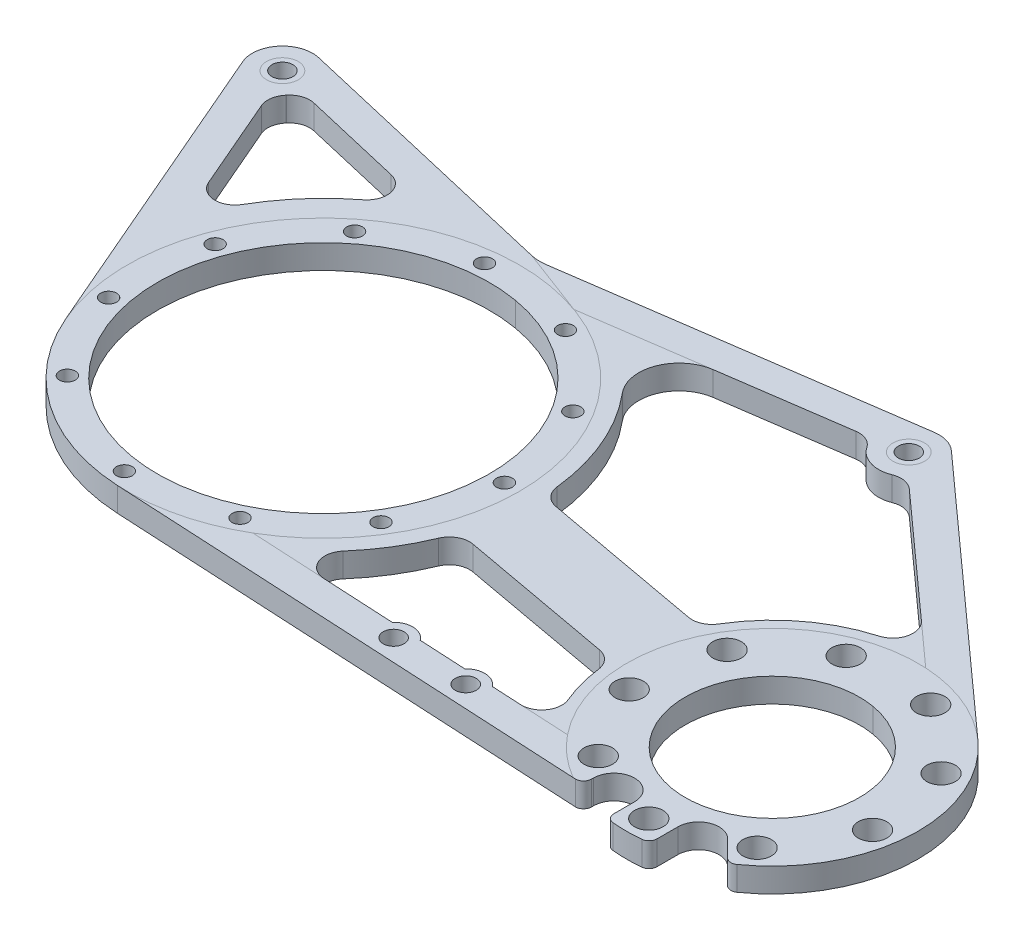
SolidWorks part; units mm, degrees
material "6061-T6 (SS)"
ref_plane "X-Y Datum" through (0, 0, 0) normal (0, 0, 1) x (1, 0, 0)
ref_plane "X-Z Datum" through (0, 0, 0) normal (0, 1, 0) x (1, 0, 0)
ref_plane "Y-Z Datum" through (0, 0, 0) normal (1, 0, 0) x (0, 0, -1)
sketch "Sketch2" plane through (0, 31.3819, 0) normal (0, 1, 0) x (1, 0, 0)
  line L0 (-693.7583, -176.702) -> (-693.7583, -183.2747) construction
  line L1 (-680.0808, -183.2747) -> (-680.0808, -176.702) construction
  line L2 (-668.9846, -172.1058) -> (-663.7197, -177.3707) construction
  line L3 (-693.7583, -176.702) -> (-693.7583, -183.2747)
  line L4 (-680.0808, -183.2747) -> (-680.0808, -176.702)
  line L5 (-668.9846, -172.1058) -> (-663.7197, -177.3707)
  line L6 (-966.641, -0.354) -> (-738.041, -0.354)
  line L7 (-727.7656, -5.5904) -> (-649.7224, -113.0358)
  line L9 (-977.8288, -19.0644) -> (-913.2312, -139.3061)
  line L10 (-706.7583, -177.279) -> (-706.7583, -176.702) construction
  line L11 (-706.7583, -177.279) -> (-706.7583, -176.702)
  line L12 (-861.9259, -171.8334) -> (-709.2983, -179.819)
  line L13 (-858.691, -110.0055) -> (-686.9195, -140.054) construction
  line L14 (-972.26, -24.9963) -> (-955.4664, -39.59) construction
  line L15 (-941.4162, -26.937) -> (-954.1775, -8.712) construction
  line L16 (-751.1929, -14.159) -> (-755.4346, -35.9995) construction
  line L17 (-737.4517, -41.8408) -> (-728.049, -21.6768) construction
  line L18 (-972.26, -24.9963) -> (-955.4664, -39.59)
  line L19 (-941.4162, -26.937) -> (-954.1775, -8.712)
  line L20 (-751.1929, -14.159) -> (-755.4346, -35.9995)
  line L21 (-737.4517, -41.8408) -> (-728.049, -21.6768)
  line L22 (-949.2186, -22.8753) -> (-746.0843, -28.2904)
  line L23 (-739.7146, -30.7335) -> (-656.1751, -105.8723)
  line L24 (-957.9647, -36.1729) -> (-915.5404, -134.527)
  arc A0 (-710.607, -179.4559) -> (-706.7583, -177.279) centre (-709.2983, -177.279) ccw construction
  arc A1 (-693.7583, -176.702) -> (-706.7583, -176.702) centre (-700.2583, -176.702) ccw construction
  arc A2 (-693.7583, -183.2747) -> (-691.4697, -185.8023) centre (-691.2183, -183.2747) ccw construction
  arc A3 (-691.4697, -185.8023) -> (-682.3694, -185.8023) centre (-686.9195, -140.054) ccw construction
  arc A4 (-682.3694, -185.8023) -> (-680.0808, -183.2747) centre (-682.6208, -183.2747) ccw construction
  arc A5 (-668.9846, -172.1058) -> (-680.0808, -176.702) centre (-673.5808, -176.702) ccw construction
  arc A6 (-663.7197, -177.3707) -> (-660.4619, -177.6519) centre (-661.9236, -175.5746) ccw construction
  arc A7 (-660.4619, -177.6519) -> (-710.607, -179.4559) centre (-686.9195, -140.054) ccw construction
  circle A8 centre (-858.691, -110.0055) radius 52.3875 construction
  circle A9 centre (-858.691, -110.0055) radius 61.9125 construction
  circle A10 centre (-738.041, -13.054) radius 12.7 construction
  circle A11 centre (-966.641, -13.054) radius 12.7 construction
  arc A12 (-710.607, -179.4559) -> (-706.7583, -177.279) centre (-709.2983, -177.279) ccw
  arc A13 (-693.7583, -176.702) -> (-706.7583, -176.702) centre (-700.2583, -176.702) ccw
  arc A14 (-693.7583, -183.2747) -> (-691.4697, -185.8023) centre (-691.2183, -183.2747) ccw
  arc A15 (-691.4697, -185.8023) -> (-682.3694, -185.8023) centre (-686.9195, -140.054) ccw
  arc A16 (-682.3694, -185.8023) -> (-680.0808, -183.2747) centre (-682.6208, -183.2747) ccw
  arc A17 (-668.9846, -172.1058) -> (-680.0808, -176.702) centre (-673.5808, -176.702) ccw
  arc A18 (-663.7197, -177.3707) -> (-660.4619, -177.6519) centre (-661.9236, -175.5746) ccw
  arc A19 (-660.4619, -177.6519) -> (-710.607, -179.4559) centre (-686.9195, -140.054) ccw
  circle A20 centre (-858.691, -110.0055) radius 52.3875
  circle A21 centre (-858.691, -110.0055) radius 61.9125
  circle A22 centre (-738.041, -13.054) radius 12.7
  circle A23 centre (-966.641, -13.054) radius 12.7
  circle A31 centre (-864.6648, -166.8424) radius 2.5 construction
  circle A39 centre (-864.6648, -166.8424) radius 2.5
  circle A40 centre (-686.9195, -140.054) radius 27.4955 construction
  circle A41 centre (-686.9195, -140.054) radius 27.4955
  circle A42 centre (-711.9883, -169.9297) radius 4.5 construction
  circle A43 centre (-725.3271, -146.8263) radius 4.5 construction
  circle A44 centre (-720.6945, -120.554) radius 4.5 construction
  circle A45 centre (-700.2583, -103.406) radius 4.5 construction
  circle A46 centre (-673.5808, -103.406) radius 4.5 construction
  circle A47 centre (-653.1446, -120.554) radius 4.5 construction
  circle A48 centre (-648.512, -146.8263) radius 4.5 construction
  circle A49 centre (-661.8508, -169.9297) radius 4.5 construction
  circle A50 centre (-686.9195, -179.054) radius 4.5 construction
  circle A51 centre (-711.9883, -169.9297) radius 4.5
  circle A52 centre (-725.3271, -146.8263) radius 4.5
  circle A53 centre (-720.6945, -120.554) radius 4.5
  circle A54 centre (-700.2583, -103.406) radius 4.5
  circle A55 centre (-673.5808, -103.406) radius 4.5
  circle A56 centre (-653.1446, -120.554) radius 4.5
  circle A57 centre (-648.512, -146.8263) radius 4.5
  circle A58 centre (-661.8508, -169.9297) radius 4.5
  circle A59 centre (-686.9195, -179.054) radius 4.5
  circle A60 centre (-966.641, -13.054) radius 3.3
  circle A61 centre (-738.041, -13.054) radius 3.3
  arc A62 (-955.4664, -39.59) -> (-941.4162, -26.937) centre (-949.2186, -32.4003) ccw construction
  arc A63 (-749.3237, -37.1863) -> (-742.8448, -38.4445) centre (-746.0843, -37.8154) ccw construction
  arc A64 (-742.8448, -38.4445) -> (-749.3237, -37.1863) centre (-746.0843, -37.8154) ccw construction
  arc A65 (-755.4346, -35.9995) -> (-737.4517, -41.8408) centre (-746.0843, -37.8154) ccw construction
  arc A66 (-955.4664, -39.59) -> (-941.4162, -26.937) centre (-949.2186, -32.4003) ccw
  arc A67 (-749.3237, -37.1863) -> (-742.8448, -38.4445) centre (-746.0843, -37.8154) ccw
  arc A68 (-742.8448, -38.4445) -> (-749.3237, -37.1863) centre (-746.0843, -37.8154) ccw
  arc A69 (-755.4346, -35.9995) -> (-737.4517, -41.8408) centre (-746.0843, -37.8154) ccw
  circle A70 centre (-949.2186, -32.4003) radius 3.3
  circle A71 centre (-949.2186, -32.4003) radius 9.525
  circle A72 centre (-746.0843, -37.8154) radius 9.525
  point P94 (-949.2186, -32.4003)
  dimension "D1" = 6.6
  dimension "D2" = 6.6
  dimension "D3" = 6.6
extrude "Boss-Extrude1" add sketch "Sketch2" along normal blind 7.62 contours A21 A39 A20 | A18 A19 A12 L11 A13 L3 A14 A15 A16 L4 A17 L5 A59 A58 A57 A56 A55 A54 A53 A52 A51 A41 | L13 A21 L12 A12 A19 | A21 L13 A19 L23 L21 A69 L20 L22 L19 A66 L18 L24 | A69 A72 A68 A67 | A72 L22 L20 | A72 L21 L23 | A71 L24 L18 | A71 L19 L22 | A71 A66 L22 A70 region at (-700.2583, 31.3819, 168.9016) region at (-773.051, 31.3819, 154.3682) region at (-890.9045, 31.3819, 160.8157) region at (-806.8861, 31.3819, 67.2042) region at (-956.9478, 31.3819, 38.0512) region at (-736.2382, 31.3819, 35.8095) region at (-956.6903, 31.3819, 37.8629) region at (-748.9437, 31.3819, 46.6182) region at (-752.4763, 31.3819, 29.8585) region at (-944.5842, 31.3819, 23.8004)
sketch "Sketch3" plane through (0, 31.3819, 0) normal (0, -1, 0) x (1, 0, 0)
  line L1 (-949.2186, 22.8753) -> (-746.0843, 28.2904) construction
  line L5 (-861.9259, 171.8334) -> (-709.2983, 179.819) construction
  line L6 (-977.8288, 19.0644) -> (-913.2312, 139.3061) construction
  line L7 (-727.7656, 5.5904) -> (-649.7224, 113.0358) construction
  line L13 (-751.1929, 14.159) -> (-755.4346, 35.9995) construction
  line L16 (-966.641, 0.354) -> (-738.041, 0.354) construction
  line L19 (-663.7197, 177.3707) -> (-668.9846, 172.1058)
  line L20 (-680.0808, 176.702) -> (-680.0808, 183.2747)
  line L21 (-693.7583, 183.2747) -> (-693.7583, 176.702)
  line L22 (-706.7583, 176.702) -> (-706.7583, 177.279)
  line L23 (-663.7197, 177.3707) -> (-668.9846, 172.1058)
  line L24 (-680.0808, 176.702) -> (-680.0808, 183.2747)
  line L25 (-693.7583, 183.2747) -> (-693.7583, 176.702)
  line L26 (-706.7583, 176.702) -> (-706.7583, 177.279)
  line L28 (-861.9259, 171.8334) -> (-709.2983, 179.819)
  line L29 (-977.8288, 19.0644) -> (-913.2312, 139.3061)
  line L30 (-727.7656, 5.5904) -> (-649.7224, 113.0358)
  line L31 (-966.641, 0.354) -> (-738.041, 0.354)
  line L34 (-737.4517, 41.8408) -> (-728.049, 21.6768) construction
  line L35 (-972.26, 24.9963) -> (-955.4664, 39.59) construction
  line L36 (-947.0539, 23.1246) -> (-856.9722, 44.1471)
  line L37 (-856.9722, 44.1471) -> (-747.4408, 28.3875)
  line L44 (-941.4162, 26.937) -> (-954.1775, 8.712) construction
  line L45 (-957.9647, 36.1729) -> (-915.5404, 134.527) construction
  line L46 (-739.7146, 30.7335) -> (-656.1751, 105.8723) construction
  line L47 (-861.9259, 171.8334) -> (-709.2983, 179.819)
  line L48 (-977.8288, 19.0644) -> (-913.2312, 139.3061)
  line L49 (-727.7656, 5.5904) -> (-649.7224, 113.0358)
  line L50 (-966.641, 0.354) -> (-738.041, 0.354)
  line L51 (-949.2186, 22.8753) -> (-746.0843, 28.2904)
  line L52 (-751.1929, 14.159) -> (-755.4346, 35.9995)
  line L53 (-737.4517, 41.8408) -> (-728.049, 21.6768)
  line L54 (-972.26, 24.9963) -> (-955.4664, 39.59)
  line L55 (-941.4162, 26.937) -> (-954.1775, 8.712)
  line L56 (-957.9647, 36.1729) -> (-915.5404, 134.527)
  line L57 (-739.7146, 30.7335) -> (-656.1751, 105.8723)
  arc A1 (-737.4517, 41.8408) -> (-755.4346, 35.9995) centre (-746.0843, 37.8154) ccw construction
  circle A3 centre (-966.641, 13.054) radius 12.7
  circle A5 centre (-966.641, 13.054) radius 12.7
  circle A7 centre (-738.041, 13.054) radius 12.7
  circle A9 centre (-738.041, 13.054) radius 12.7
  circle A11 centre (-858.691, 110.0055) radius 61.9125
  circle A13 centre (-858.691, 110.0055) radius 61.9125
  circle A15 centre (-858.691, 110.0055) radius 52.3875
  circle A17 centre (-858.691, 110.0055) radius 52.3875
  circle A19 centre (-686.9195, 140.054) radius 27.4955
  circle A21 centre (-686.9195, 140.054) radius 27.4955
  circle A23 centre (-864.6648, 166.8424) radius 2.5
  circle A25 centre (-864.6648, 166.8424) radius 2.5
  circle A51 centre (-720.6945, 120.554) radius 4.5
  circle A52 centre (-720.6945, 120.554) radius 4.5
  circle A68 centre (-725.3271, 146.8263) radius 4.5
  circle A69 centre (-725.3271, 146.8263) radius 4.5
  circle A70 centre (-711.9883, 169.9297) radius 4.5
  circle A71 centre (-711.9883, 169.9297) radius 4.5
  circle A72 centre (-738.041, 13.054) radius 3.3
  circle A73 centre (-738.041, 13.054) radius 3.3
  circle A74 centre (-966.641, 13.054) radius 3.3
  circle A75 centre (-966.641, 13.054) radius 3.3
  circle A76 centre (-686.9195, 179.054) radius 4.5
  circle A77 centre (-686.9195, 179.054) radius 4.5
  circle A78 centre (-661.8508, 169.9297) radius 4.5
  circle A79 centre (-661.8508, 169.9297) radius 4.5
  circle A80 centre (-648.512, 146.8263) radius 4.5
  circle A81 centre (-648.512, 146.8263) radius 4.5
  circle A82 centre (-653.1446, 120.554) radius 4.5
  circle A83 centre (-653.1446, 120.554) radius 4.5
  circle A84 centre (-673.5808, 103.406) radius 4.5
  circle A85 centre (-673.5808, 103.406) radius 4.5
  circle A86 centre (-700.2583, 103.406) radius 4.5
  circle A87 centre (-700.2583, 103.406) radius 4.5
  arc A95 (-710.607, 179.4559) -> (-660.4619, 177.6519) centre (-686.9195, 140.054) ccw
  arc A96 (-660.4619, 177.6519) -> (-663.7197, 177.3707) centre (-661.9236, 175.5746) ccw
  arc A97 (-680.0808, 176.702) -> (-668.9846, 172.1058) centre (-673.5808, 176.702) ccw
  arc A98 (-680.0808, 183.2747) -> (-682.3694, 185.8023) centre (-682.6208, 183.2747) ccw
  arc A99 (-682.3694, 185.8023) -> (-691.4697, 185.8023) centre (-686.9195, 140.054) ccw
  arc A100 (-691.4697, 185.8023) -> (-693.7583, 183.2747) centre (-691.2183, 183.2747) ccw
  arc A101 (-706.7583, 176.702) -> (-693.7583, 176.702) centre (-700.2583, 176.702) ccw
  arc A102 (-706.7583, 177.279) -> (-710.607, 179.4559) centre (-709.2983, 177.279) ccw
  arc A103 (-710.607, 179.4559) -> (-660.4619, 177.6519) centre (-686.9195, 140.054) ccw
  arc A104 (-660.4619, 177.6519) -> (-663.7197, 177.3707) centre (-661.9236, 175.5746) ccw
  arc A105 (-680.0808, 176.702) -> (-668.9846, 172.1058) centre (-673.5808, 176.702) ccw
  arc A106 (-680.0808, 183.2747) -> (-682.3694, 185.8023) centre (-682.6208, 183.2747) ccw
  arc A107 (-682.3694, 185.8023) -> (-691.4697, 185.8023) centre (-686.9195, 140.054) ccw
  arc A108 (-691.4697, 185.8023) -> (-693.7583, 183.2747) centre (-691.2183, 183.2747) ccw
  arc A109 (-706.7583, 176.702) -> (-693.7583, 176.702) centre (-700.2583, 176.702) ccw
  arc A110 (-706.7583, 177.279) -> (-710.607, 179.4559) centre (-709.2983, 177.279) ccw
  circle A152 centre (-746.0843, 37.8154) radius 9.525
  circle A153 centre (-746.0843, 37.8154) radius 9.525
  circle A154 centre (-949.2186, 32.4003) radius 9.525
  circle A155 centre (-949.2186, 32.4003) radius 9.525
  circle A156 centre (-949.2186, 32.4003) radius 3.3
  circle A157 centre (-949.2186, 32.4003) radius 3.3
  arc A158 (-941.4162, 26.937) -> (-955.4664, 39.59) centre (-949.2186, 32.4003) ccw construction
  arc A159 (-742.8448, 38.4445) -> (-749.3237, 37.1863) centre (-746.0843, 37.8154) ccw
  arc A160 (-749.3237, 37.1863) -> (-742.8448, 38.4445) centre (-746.0843, 37.8154) ccw
  arc A161 (-742.8448, 38.4445) -> (-749.3237, 37.1863) centre (-746.0843, 37.8154) ccw
  arc A162 (-749.3237, 37.1863) -> (-742.8448, 38.4445) centre (-746.0843, 37.8154) ccw
  arc A163 (-737.4517, 41.8408) -> (-755.4346, 35.9995) centre (-746.0843, 37.8154) ccw
  arc A164 (-941.4162, 26.937) -> (-955.4664, 39.59) centre (-949.2186, 32.4003) ccw
  dimension "D24" = 0
  dimension "D25" = 0
  dimension "D26" = 90.0818
  dimension "D27" = 21.0225
  dimension "D1" = 0
  dimension "D2" = 0
  dimension "D3" = 0
  dimension "D4" = 0
  dimension "D5" = 0
  dimension "D6" = 0
  dimension "D14" = 0
  dimension "D15" = 0
  dimension "D16" = 0
  dimension "D17" = 0
  dimension "D18" = 0
  dimension "D19" = 0
  dimension "D20" = 0
  dimension "D21" = 0
  dimension "D22" = 0
  dimension "D23" = 0
  dimension "D52" = 0
  dimension "D53" = 0
  dimension "D54" = 0
  dimension "D55" = 0
ref_point "Point1"
ref_point "Point2"
ref_plane "Plane1" through (-858.691, 31.3819, 110.0055) normal (0.985, 0, 0.1723) x (0.1723, 0, -0.985)
ref_plane "Plane2" through (-686.9195, 31.3819, 140.054) normal (-0.985, 0, -0.1723) x (-0.1723, 0, 0.985)
split line "Split Line1"
split line "Split Line2"
ref_axis "Axis1" through (-858.691, 39.0019, 110.0055) along (0, -1, 0)
ref_axis "Axis2" through (-686.9195, 39.0019, 140.054) along (0, -1, 0)
extrude "Cut-Extrude1" cut sketch "Sketch3" against normal through all contours L36 L55 L51 L52 L37 | A155 L51 L55 L36 | A153 L37 L52 L51 region at (-751.5495, 31.3819, 28.5688) region at (-850.6911, 31.3819, 31.7926) region at (-945.2616, 31.3819, 23.2848)
fillet "Fillet2" radius 12.7 1 edges at (-856.9722, 35.1919, 44.1471)
sketch "Sketch4" plane through (0, 31.3819, 0) normal (0, -1, 0) x (1, 0, 0)
  line L0 (-861.9259, 171.8334) -> (-709.2983, 179.819) construction
  line L1 (-727.7656, 5.5904) -> (-649.7224, 113.0358) construction
  line L2 (-977.8288, 19.0644) -> (-913.2312, 139.3061) construction
  line L4 (-706.7583, 176.702) -> (-706.7583, 177.279)
  line L5 (-663.7197, 177.3707) -> (-668.9846, 172.1058)
  line L6 (-680.0808, 176.702) -> (-680.0808, 183.2747)
  line L7 (-693.7583, 183.2747) -> (-693.7583, 176.702)
  line L8 (-706.7583, 176.702) -> (-706.7583, 177.279)
  line L9 (-663.7197, 177.3707) -> (-668.9846, 172.1058)
  line L10 (-680.0808, 176.702) -> (-680.0808, 183.2747)
  line L11 (-693.7583, 183.2747) -> (-693.7583, 176.702)
  line L13 (-966.641, 0.354) -> (-738.041, 0.354) construction
  line L14 (-861.9259, 171.8334) -> (-709.2983, 179.819)
  line L15 (-727.7656, 5.5904) -> (-649.7224, 113.0358)
  line L16 (-977.8288, 19.0644) -> (-913.2312, 139.3061)
  line L17 (-861.9259, 171.8334) -> (-709.2983, 179.819) construction
  line L19 (-966.641, 0.354) -> (-738.041, 0.354)
  line L20 (-924.6037, 87.863) -> (-948.1369, 33.3048)
  line L21 (-948.1369, 33.3048) -> (-888.5504, 47.2106)
  line L22 (-732.3805, 168.4374) -> (-812.7818, 164.2308) construction
  line L23 (-812.7818, 164.2308) -> (-733.9678, 114.3873) construction
  line L24 (-799.833, 147.0258) -> (-703.8013, 86.2934) construction
  line L25 (-703.8013, 86.2934) -> (-794.9695, 82.1785) construction
  line L26 (-824.108, 49.6832) -> (-755.4008, 39.7974) construction
  line L27 (-798.9847, 74.3695) -> (-701.5009, 78.7695) construction
  line L28 (-701.5009, 78.7695) -> (-739.4428, 44.643) construction
  line L29 (-977.8288, 19.0644) -> (-913.2312, 139.3061) construction
  line L30 (-727.7656, 5.5904) -> (-649.7224, 113.0358) construction
  line L31 (-966.641, 0.354) -> (-738.041, 0.354) construction
  line L32 (-663.7197, 177.3707) -> (-668.9846, 172.1058)
  line L33 (-680.0808, 176.702) -> (-680.0808, 183.2747)
  line L34 (-693.7583, 183.2747) -> (-693.7583, 176.702)
  line L35 (-706.7583, 176.702) -> (-706.7583, 177.279)
  line L36 (-663.7197, 177.3707) -> (-668.9846, 172.1058)
  line L37 (-680.0808, 176.702) -> (-680.0808, 183.2747)
  line L38 (-693.7583, 183.2747) -> (-693.7583, 176.702)
  line L39 (-706.7583, 176.702) -> (-706.7583, 177.279)
  line L40 (-949.2186, 22.8753) -> (-746.0843, 28.2904) construction
  line L41 (-751.1929, 14.159) -> (-755.4346, 35.9995) construction
  line L42 (-737.4517, 41.8408) -> (-728.049, 21.6768) construction
  line L43 (-972.26, 24.9963) -> (-955.4664, 39.59) construction
  line L44 (-941.4162, 26.937) -> (-954.1775, 8.712) construction
  line L45 (-957.9647, 36.1729) -> (-915.5404, 134.527) construction
  line L46 (-739.7146, 30.7335) -> (-656.1751, 105.8723) construction
  line L47 (-861.9259, 171.8334) -> (-709.2983, 179.819)
  line L48 (-977.8288, 19.0644) -> (-913.2312, 139.3061)
  line L49 (-727.7656, 5.5904) -> (-649.7224, 113.0358)
  line L50 (-966.641, 0.354) -> (-738.041, 0.354)
  line L51 (-949.2186, 22.8753) -> (-746.0843, 28.2904)
  line L52 (-751.1929, 14.159) -> (-755.4346, 35.9995)
  line L53 (-737.4517, 41.8408) -> (-728.049, 21.6768)
  line L54 (-972.26, 24.9963) -> (-955.4664, 39.59)
  line L55 (-941.4162, 26.937) -> (-954.1775, 8.712)
  line L56 (-957.9647, 36.1729) -> (-915.5404, 134.527)
  line L57 (-739.7146, 30.7335) -> (-656.1751, 105.8723)
  line L58 (-947.0539, 23.1246) -> (-859.3005, 43.6037) construction
  line L60 (-854.6056, 43.8066) -> (-747.4408, 28.3875) construction
  circle A1 centre (-858.691, 110.0055) radius 52.3875
  circle A2 centre (-858.691, 110.0055) radius 52.3875
  circle A3 centre (-858.691, 110.0055) radius 61.9125
  circle A4 centre (-858.691, 110.0055) radius 61.9125
  circle A5 centre (-738.041, 13.054) radius 12.7
  circle A6 centre (-738.041, 13.054) radius 12.7
  circle A7 centre (-966.641, 13.054) radius 12.7
  circle A8 centre (-966.641, 13.054) radius 12.7
  circle A17 centre (-864.6648, 166.8424) radius 2.5
  circle A18 centre (-864.6648, 166.8424) radius 2.5
  circle A19 centre (-686.9195, 140.054) radius 27.4955
  circle A20 centre (-686.9195, 140.054) radius 27.4955
  circle A21 centre (-725.3271, 146.8263) radius 4.5
  circle A22 centre (-725.3271, 146.8263) radius 4.5
  circle A23 centre (-720.6945, 120.554) radius 4.5
  circle A24 centre (-720.6945, 120.554) radius 4.5
  circle A31 centre (-661.8508, 169.9297) radius 4.5
  circle A32 centre (-661.8508, 169.9297) radius 4.5
  circle A33 centre (-686.9195, 179.054) radius 4.5
  circle A34 centre (-686.9195, 179.054) radius 4.5
  circle A35 centre (-966.641, 13.054) radius 3.3
  circle A36 centre (-966.641, 13.054) radius 3.3
  circle A37 centre (-738.041, 13.054) radius 3.3
  circle A38 centre (-738.041, 13.054) radius 3.3
  circle A39 centre (-711.9883, 169.9297) radius 4.5
  circle A40 centre (-711.9883, 169.9297) radius 4.5
  circle A41 centre (-700.2583, 103.406) radius 4.5
  circle A42 centre (-700.2583, 103.406) radius 4.5
  circle A43 centre (-673.5808, 103.406) radius 4.5
  circle A44 centre (-673.5808, 103.406) radius 4.5
  circle A45 centre (-653.1446, 120.554) radius 4.5
  circle A46 centre (-653.1446, 120.554) radius 4.5
  circle A47 centre (-648.512, 146.8263) radius 4.5
  circle A48 centre (-648.512, 146.8263) radius 4.5
  arc A49 (-888.5504, 47.2106) -> (-924.6037, 87.863) centre (-858.691, 110.0055) cw
  arc A50 (-732.3805, 168.4374) -> (-733.9678, 114.3873) centre (-686.9195, 140.054) ccw construction
  arc A51 (-799.833, 147.0258) -> (-794.9695, 82.1785) centre (-858.691, 110.0055) cw construction
  arc A52 (-824.108, 49.6832) -> (-798.9847, 74.3695) centre (-858.691, 110.0055) ccw construction
  arc A53 (-737.4517, 41.8408) -> (-755.4346, 35.9995) centre (-746.0843, 37.8154) ccw construction
  circle A54 centre (-966.641, 13.054) radius 12.7
  circle A55 centre (-966.641, 13.054) radius 12.7
  arc A56 (-706.7583, 177.279) -> (-710.607, 179.4559) centre (-709.2983, 177.279) ccw
  arc A57 (-710.607, 179.4559) -> (-660.4619, 177.6519) centre (-686.9195, 140.054) ccw
  arc A58 (-660.4619, 177.6519) -> (-663.7197, 177.3707) centre (-661.9236, 175.5746) ccw
  arc A59 (-680.0808, 176.702) -> (-668.9846, 172.1058) centre (-673.5808, 176.702) ccw
  arc A60 (-680.0808, 183.2747) -> (-682.3694, 185.8023) centre (-682.6208, 183.2747) ccw
  arc A61 (-682.3694, 185.8023) -> (-691.4697, 185.8023) centre (-686.9195, 140.054) ccw
  arc A62 (-691.4697, 185.8023) -> (-693.7583, 183.2747) centre (-691.2183, 183.2747) ccw
  arc A63 (-706.7583, 176.702) -> (-693.7583, 176.702) centre (-700.2583, 176.702) ccw
  arc A64 (-706.7583, 177.279) -> (-710.607, 179.4559) centre (-709.2983, 177.279) ccw
  arc A65 (-710.607, 179.4559) -> (-660.4619, 177.6519) centre (-686.9195, 140.054) ccw
  arc A66 (-660.4619, 177.6519) -> (-663.7197, 177.3707) centre (-661.9236, 175.5746) ccw
  arc A67 (-680.0808, 176.702) -> (-668.9846, 172.1058) centre (-673.5808, 176.702) ccw
  arc A68 (-680.0808, 183.2747) -> (-682.3694, 185.8023) centre (-682.6208, 183.2747) ccw
  arc A69 (-682.3694, 185.8023) -> (-691.4697, 185.8023) centre (-686.9195, 140.054) ccw
  arc A70 (-691.4697, 185.8023) -> (-693.7583, 183.2747) centre (-691.2183, 183.2747) ccw
  arc A71 (-706.7583, 176.702) -> (-693.7583, 176.702) centre (-700.2583, 176.702) ccw
  circle A72 centre (-738.041, 13.054) radius 12.7
  circle A73 centre (-738.041, 13.054) radius 12.7
  circle A74 centre (-858.691, 110.0055) radius 61.9125
  circle A75 centre (-858.691, 110.0055) radius 61.9125
  circle A76 centre (-858.691, 110.0055) radius 52.3875
  circle A77 centre (-858.691, 110.0055) radius 52.3875
  circle A78 centre (-686.9195, 140.054) radius 27.4955
  circle A79 centre (-686.9195, 140.054) radius 27.4955
  circle A80 centre (-864.6648, 166.8424) radius 2.5
  circle A81 centre (-864.6648, 166.8424) radius 2.5
  circle A96 centre (-720.6945, 120.554) radius 4.5
  circle A97 centre (-720.6945, 120.554) radius 4.5
  circle A98 centre (-725.3271, 146.8263) radius 4.5
  circle A99 centre (-725.3271, 146.8263) radius 4.5
  circle A100 centre (-711.9883, 169.9297) radius 4.5
  circle A101 centre (-711.9883, 169.9297) radius 4.5
  circle A102 centre (-738.041, 13.054) radius 3.3
  circle A103 centre (-738.041, 13.054) radius 3.3
  circle A104 centre (-966.641, 13.054) radius 3.3
  circle A105 centre (-966.641, 13.054) radius 3.3
  circle A106 centre (-686.9195, 179.054) radius 4.5
  circle A107 centre (-686.9195, 179.054) radius 4.5
  circle A108 centre (-661.8508, 169.9297) radius 4.5
  circle A109 centre (-661.8508, 169.9297) radius 4.5
  circle A110 centre (-648.512, 146.8263) radius 4.5
  circle A111 centre (-648.512, 146.8263) radius 4.5
  circle A112 centre (-653.1446, 120.554) radius 4.5
  circle A113 centre (-653.1446, 120.554) radius 4.5
  circle A114 centre (-673.5808, 103.406) radius 4.5
  circle A115 centre (-673.5808, 103.406) radius 4.5
  circle A116 centre (-700.2583, 103.406) radius 4.5
  circle A117 centre (-700.2583, 103.406) radius 4.5
  circle A118 centre (-746.0843, 37.8154) radius 9.525
  circle A119 centre (-746.0843, 37.8154) radius 9.525
  circle A120 centre (-949.2186, 32.4003) radius 9.525
  circle A121 centre (-949.2186, 32.4003) radius 9.525
  circle A122 centre (-949.2186, 32.4003) radius 3.3
  circle A123 centre (-949.2186, 32.4003) radius 3.3
  arc A124 (-941.4162, 26.937) -> (-955.4664, 39.59) centre (-949.2186, 32.4003) ccw construction
  arc A125 (-742.8448, 38.4445) -> (-749.3237, 37.1863) centre (-746.0843, 37.8154) ccw
  arc A126 (-749.3237, 37.1863) -> (-742.8448, 38.4445) centre (-746.0843, 37.8154) ccw
  arc A127 (-742.8448, 38.4445) -> (-749.3237, 37.1863) centre (-746.0843, 37.8154) ccw
  arc A128 (-749.3237, 37.1863) -> (-742.8448, 38.4445) centre (-746.0843, 37.8154) ccw
  arc A129 (-737.4517, 41.8408) -> (-755.4346, 35.9995) centre (-746.0843, 37.8154) ccw
  arc A130 (-941.4162, 26.937) -> (-955.4664, 39.59) centre (-949.2186, 32.4003) ccw
  arc A135 (-710.607, 179.4559) -> (-660.4619, 177.6519) centre (-686.9195, 140.054) ccw
  arc A136 (-660.4619, 177.6519) -> (-663.7197, 177.3707) centre (-661.9236, 175.5746) ccw
  arc A137 (-680.0808, 176.702) -> (-668.9846, 172.1058) centre (-673.5808, 176.702) ccw
  arc A138 (-680.0808, 183.2747) -> (-682.3694, 185.8023) centre (-682.6208, 183.2747) ccw
  arc A139 (-682.3694, 185.8023) -> (-691.4697, 185.8023) centre (-686.9195, 140.054) ccw
  arc A140 (-691.4697, 185.8023) -> (-693.7583, 183.2747) centre (-691.2183, 183.2747) ccw
  arc A141 (-706.7583, 176.702) -> (-693.7583, 176.702) centre (-700.2583, 176.702) ccw
  arc A142 (-706.7583, 177.279) -> (-710.607, 179.4559) centre (-709.2983, 177.279) ccw
  arc A143 (-710.607, 179.4559) -> (-660.4619, 177.6519) centre (-686.9195, 140.054) ccw
  arc A144 (-660.4619, 177.6519) -> (-663.7197, 177.3707) centre (-661.9236, 175.5746) ccw
  arc A145 (-680.0808, 176.702) -> (-668.9846, 172.1058) centre (-673.5808, 176.702) ccw
  arc A146 (-680.0808, 183.2747) -> (-682.3694, 185.8023) centre (-682.6208, 183.2747) ccw
  arc A147 (-682.3694, 185.8023) -> (-691.4697, 185.8023) centre (-686.9195, 140.054) ccw
  arc A148 (-691.4697, 185.8023) -> (-693.7583, 183.2747) centre (-691.2183, 183.2747) ccw
  arc A149 (-706.7583, 176.702) -> (-693.7583, 176.702) centre (-700.2583, 176.702) ccw
  arc A150 (-706.7583, 177.279) -> (-710.607, 179.4559) centre (-709.2983, 177.279) ccw
  dimension "D26" = 7.62
  dimension "D29" = 7.62
  dimension "D30" = 7.62
  dimension "D35" = 0
  dimension "D39" = 7.62
  dimension "D27" = 0
  dimension "D28" = 0
  dimension "D31" = 10.16
  dimension "D32" = 7.62
  dimension "D33" = 93.2524
  dimension "D34" = 49.8435
  dimension "D36" = 91.1683
  dimension "D37" = 4.1149
  dimension "D38" = 10.16
  dimension "D40" = 7.62
  dimension "D67" = 10.16
  dimension "D68" = 10.16
  dimension "D69" = 10.16
  dimension "D1" = 0
  dimension "D2" = 0
  dimension "D3" = 0
  dimension "D4" = 0
  dimension "D9" = 0
  dimension "D10" = 0
  dimension "D11" = 0
  dimension "D12" = 0
  dimension "D16" = 0
  dimension "D17" = 0
  dimension "D18" = 0
  dimension "D19" = 0
  dimension "D20" = 0
  dimension "D21" = 0
  dimension "D22" = 0
  dimension "D23" = 0
  dimension "D24" = 0
  dimension "D25" = 0
  dimension "D41" = 0
  dimension "D42" = 0
  dimension "D43" = 0
  dimension "D51" = 0
  dimension "D52" = 0
  dimension "D53" = 0
  dimension "D54" = 0
  dimension "D55" = 0
  dimension "D56" = 0
  dimension "D57" = 0
  dimension "D58" = 0
  dimension "D59" = 0
  dimension "D60" = 0
  dimension "D61" = 0
  dimension "D62" = 0
  dimension "D63" = 0
  dimension "D64" = 0
  dimension "D65" = 0
  dimension "D66" = 0
extrude "Cut-Extrude2" cut sketch "Sketch4" against normal through all contours L21 A49 L20 A8 | A52 L26 A6 L28 L27 | L24 A51 L25 | A50 L22 L23 region at (-829.4195, 31.3819, 24.9298) region at (-921.8341, 31.3819, 54.9859)
split line "Split Line3"
sketch "Sketch2<4>" plane through (0, 31.3819, 0) normal (0, 1, 0) x (1, 0, 0) same geometry as "Sketch2"
pattern_circular "CirPattern2" count 11 every 32 about axis through (-858.691, 39.0019, 110.0055) along (0, -1, 0) reverse direction yes of face at (-867.1648, 39.0019, 166.8424)
sketch "Sketch5" plane through (0, 39.0019, 0) normal (0, 1, 0) x (1, 0, 0)
  circle A0 centre (-949.2186, -32.4003) radius 5
  circle A1 centre (-746.0843, -37.8154) radius 5
  dimension "D1" = 10
split line "Split Line4"
sketch "Sketch7" plane through (0, 31.3819, 0) normal (0, -1, 0) x (1, 0, 0)
  line L0 (-859.3005, 43.6037) -> (-836.8375, 52.0781)
  arc A0 (-915.5404, 134.527) -> (-861.9259, 171.8334) centre (-858.691, 110.0055) ccw construction
split line "Split Line5"
sketch "Sketch8" plane through (0, 39.0019, 0) normal (0, 1, 0) x (1, 0, 0)
  line L0 (-859.3005, -43.6037) -> (-836.8375, -52.0781) construction
  line L1 (-859.3005, -43.6037) -> (-836.8375, -52.0781)
  line L2 (-732.3805, -168.4374) -> (-812.7818, -164.2308) construction
  line L3 (-824.108, -49.6832) -> (-755.4008, -39.7974) construction
  line L4 (-701.5009, -78.7695) -> (-739.4428, -44.643) construction
  line L5 (-732.3805, -168.4374) -> (-812.7818, -164.2308)
  line L6 (-824.108, -49.6832) -> (-755.4008, -39.7974)
  line L7 (-709.5634, -179.8051) -> (-709.2983, -179.819)
  line L8 (-668.9846, -172.1058) -> (-663.7197, -177.3707)
  line L9 (-680.0808, -183.2747) -> (-680.0808, -176.702)
  line L10 (-693.7583, -176.702) -> (-693.7583, -183.2747)
  line L11 (-706.7583, -177.279) -> (-706.7583, -176.702)
  line L12 (-709.5634, -179.8051) -> (-709.2983, -179.819)
  line L13 (-668.9846, -172.1058) -> (-663.7197, -177.3707)
  line L14 (-680.0808, -183.2747) -> (-680.0808, -176.702)
  line L15 (-693.7583, -176.702) -> (-693.7583, -183.2747)
  line L16 (-706.7583, -177.279) -> (-706.7583, -176.702)
  line L17 (-701.5009, -78.7695) -> (-739.4428, -44.643)
  line L18 (-701.5009, -78.7695) -> (-684.402, -94.149)
  line L19 (-824.108, -49.6832) -> (-837.9186, -51.6702)
  line L20 (-732.3805, -168.4374) -> (-722.6816, -168.9449)
  line L21 (-812.7818, -164.2308) -> (-827.4586, -163.4628)
  circle A0 centre (-746.0843, -37.8154) radius 9.525 construction
  circle A1 centre (-746.0843, -37.8154) radius 9.525 construction
  arc A2 (-739.4428, -44.643) -> (-755.4008, -39.7974) centre (-746.0843, -37.8154) cw
  arc A3 (-915.5404, -134.527) -> (-861.9259, -171.8334) centre (-858.691, -110.0055) ccw
  arc A4 (-836.8375, -52.0781) -> (-915.5404, -134.527) centre (-858.691, -110.0055) ccw
  arc A5 (-861.9259, -171.8334) -> (-836.8375, -52.0781) centre (-858.691, -110.0055) ccw
  arc A6 (-915.5404, -134.527) -> (-861.9259, -171.8334) centre (-858.691, -110.0055) ccw
  arc A7 (-836.8375, -52.0781) -> (-915.5404, -134.527) centre (-858.691, -110.0055) ccw
  arc A8 (-861.9259, -171.8334) -> (-836.8375, -52.0781) centre (-858.691, -110.0055) ccw
  arc A16 (-710.607, -179.4559) -> (-709.5634, -179.8051) centre (-709.2983, -177.279) ccw
  arc A17 (-656.1751, -105.8723) -> (-710.607, -179.4559) centre (-686.9195, -140.054) ccw
  arc A18 (-660.4619, -177.6519) -> (-656.1751, -105.8723) centre (-686.9195, -140.054) ccw
  arc A19 (-663.7197, -177.3707) -> (-660.4619, -177.6519) centre (-661.9236, -175.5746) ccw
  arc A20 (-668.9846, -172.1058) -> (-680.0808, -176.702) centre (-673.5808, -176.702) ccw
  arc A21 (-682.3694, -185.8023) -> (-680.0808, -183.2747) centre (-682.6208, -183.2747) ccw
  arc A22 (-691.4697, -185.8023) -> (-682.3694, -185.8023) centre (-686.9195, -140.054) ccw
  arc A23 (-693.7583, -183.2747) -> (-691.4697, -185.8023) centre (-691.2183, -183.2747) ccw
  arc A24 (-693.7583, -176.702) -> (-706.7583, -176.702) centre (-700.2583, -176.702) ccw
  arc A25 (-709.2983, -179.819) -> (-706.7583, -177.279) centre (-709.2983, -177.279) ccw
  arc A26 (-710.607, -179.4559) -> (-709.5634, -179.8051) centre (-709.2983, -177.279) ccw
  arc A27 (-656.1751, -105.8723) -> (-710.607, -179.4559) centre (-686.9195, -140.054) ccw
  arc A28 (-660.4619, -177.6519) -> (-656.1751, -105.8723) centre (-686.9195, -140.054) ccw
  arc A29 (-663.7197, -177.3707) -> (-660.4619, -177.6519) centre (-661.9236, -175.5746) ccw
  arc A30 (-668.9846, -172.1058) -> (-680.0808, -176.702) centre (-673.5808, -176.702) ccw
  arc A31 (-682.3694, -185.8023) -> (-680.0808, -183.2747) centre (-682.6208, -183.2747) ccw
  arc A32 (-691.4697, -185.8023) -> (-682.3694, -185.8023) centre (-686.9195, -140.054) ccw
  arc A33 (-693.7583, -183.2747) -> (-691.4697, -185.8023) centre (-691.2183, -183.2747) ccw
  arc A34 (-693.7583, -176.702) -> (-706.7583, -176.702) centre (-700.2583, -176.702) ccw
  arc A35 (-709.2983, -179.819) -> (-706.7583, -177.279) centre (-709.2983, -177.279) ccw
  dimension "D1" = 0
  dimension "D2" = 0
split line "Split Line6"
fillet "Fillet4" radius 6.3754 4 edges at (-940.1078, 35.1919, 35.1786) (-944.8714, 35.1919, 40.8754) (-888.5504, 35.1919, 47.2106) (-924.6037, 35.1919, 87.863)
sketch "Sketch9" plane through (0, 31.3819, 0) normal (0, -1, 0) x (1, 0, 0)
  line L8 (-732.3805, 168.4374) -> (-812.7818, 164.2308)
  line L9 (-722.6816, 168.9449) -> (-732.3805, 168.4374)
  line L10 (-701.5009, 78.7695) -> (-684.402, 94.149)
  line L11 (-739.4428, 44.643) -> (-701.5009, 78.7695)
  line L12 (-824.108, 49.6832) -> (-755.4008, 39.7974)
  line L13 (-837.9186, 51.6702) -> (-824.108, 49.6832)
  line L14 (-836.8375, 52.0781) -> (-837.9186, 51.6702)
  line L15 (-812.7818, 164.2308) -> (-827.4586, 163.4628)
  line L16 (-732.3805, 168.4374) -> (-812.7818, 164.2308)
  line L17 (-722.6816, 168.9449) -> (-732.3805, 168.4374)
  line L18 (-701.5009, 78.7695) -> (-684.402, 94.149)
  line L19 (-739.4428, 44.643) -> (-701.5009, 78.7695)
  line L20 (-824.108, 49.6832) -> (-755.4008, 39.7974)
  line L21 (-837.9186, 51.6702) -> (-824.108, 49.6832)
  line L22 (-836.8375, 52.0781) -> (-837.9186, 51.6702)
  line L23 (-812.7818, 164.2308) -> (-827.4586, 163.4628)
  arc A3 (-722.6816, 168.9449) -> (-684.402, 94.149) centre (-686.9195, 140.054) ccw
  arc A4 (-739.4428, 44.643) -> (-755.4008, 39.7974) centre (-746.0843, 37.8154) ccw
  arc A5 (-836.8375, 52.0781) -> (-827.4586, 163.4628) centre (-858.691, 110.0055) ccw
  arc A6 (-722.6816, 168.9449) -> (-684.402, 94.149) centre (-686.9195, 140.054) ccw
  arc A7 (-739.4428, 44.643) -> (-755.4008, 39.7974) centre (-746.0843, 37.8154) ccw
  arc A8 (-836.8375, 52.0781) -> (-827.4586, 163.4628) centre (-858.691, 110.0055) ccw
  dimension "D1" = 0
split line "Split Line7"
sketch "Sketch10" plane through (0, 31.3819, 0) normal (0, -1, 0) x (1, 0, 0)
  line L0 (-818.9129, 163.91) -> (-726.8377, 168.7274)
  line L1 (-732.3805, 168.4374) -> (-812.7818, 164.2308) construction
  line L2 (-837.9186, 51.6702) -> (-824.108, 49.6832) construction
  line L3 (-812.7818, 164.2308) -> (-827.4586, 163.4628) construction
  line L4 (-798.0516, 122.496) -> (-732.5518, 134.4586) construction
  line L5 (-795.007, 130.7981) -> (-736.0453, 141.5666)
  line L6 (-791.745, 107.5102) -> (-731.1295, 118.5807)
  line L7 (-701.5009, 78.7695) -> (-684.402, 94.149) construction
  line L8 (-828.3256, 50.29) -> (-755.4008, 39.7974)
  line L9 (-739.4428, 44.643) -> (-687.9956, 90.9168)
  arc A0 (-828.3256, 50.29) -> (-791.745, 107.5102) centre (-858.691, 110.0055) ccw
  arc A1 (-731.1295, 118.5807) -> (-687.9956, 90.9168) centre (-686.9195, 140.054) ccw
  arc A2 (-818.9129, 163.91) -> (-795.007, 130.7981) centre (-858.691, 110.0055) cw
  arc A3 (-835.0444, 47.3251) -> (-824.896, 167.8491) centre (-858.691, 110.0055) ccw
  arc A4 (-835.0444, 47.3251) -> (-824.896, 167.8491) centre (-858.691, 110.0055) ccw construction
  arc A5 (-836.8375, 52.0781) -> (-827.4586, 163.4628) centre (-858.691, 110.0055) ccw construction
  arc A6 (-722.6816, 168.9449) -> (-684.402, 94.149) centre (-686.9195, 140.054) ccw construction
  arc A7 (-726.8377, 168.7274) -> (-736.0453, 141.5666) centre (-686.9195, 140.054) ccw
  arc A8 (-725.1514, 170.9401) -> (-684.2281, 90.9787) centre (-686.9195, 140.054) ccw
  arc A9 (-725.1514, 170.9401) -> (-684.2281, 90.9787) centre (-686.9195, 140.054) ccw construction
  arc A10 (-755.4008, 39.7974) -> (-739.4428, 44.643) centre (-746.0843, 37.8154) cw
  arc A11 (-739.4428, 44.643) -> (-755.4008, 39.7974) centre (-746.0843, 37.8154) ccw construction
  dimension "D3" = 41.4139
  dimension "D4" = 34.2689
  dimension "D5" = 7.62
  dimension "D6" = 15.875
  dimension "D1" = 5.08
  dimension "D2" = 3.175
extrude "Cut-Extrude4" cut sketch "Sketch10" against normal through all contours L5 A7 L0 A2 | L9 A1 L6 A0 L8 A10
fillet "Fillet5" radius 6.3754 8 edges at (-687.9956, 35.1919, 90.9168) (-739.4428, 35.1919, 44.643) (-755.4008, 35.1919, 39.7974) (-731.1295, 35.1919, 118.5807) (-795.007, 35.1919, 130.7981) (-736.0453, 35.1919, 141.5666) (-726.8377, 35.1919, 168.7274) (-818.9129, 35.1919, 163.91)
fillet "Fillet6" radius 6.3754 1 edges at (-791.745, 35.1919, 107.5102)
fillet "Fillet7" radius 12.7 1 edges at (-828.3256, 35.1919, 50.29)
sketch3d "3DSketch1"
  arc A3 (-738.3594, 31.3819, 168.1246) -> (-732.1581, 31.3819, 159.2658) centre (-738.0263, 31.3819, 161.7579) ccw construction
  arc A4 (-732.1581, 31.3819, 159.2658) -> (-735.6872, 31.3819, 146.1648) centre (-686.9195, 31.3819, 140.054) ccw
  arc A5 (-738.3594, 31.3819, 168.1246) -> (-732.1581, 31.3819, 159.2658) centre (-738.0263, 31.3819, 161.7579) ccw
  circle A6 centre (-752.529, 24.9199, 171.23) radius 5 construction
  circle A7 centre (-776.621, 24.7819, 169.8829) radius 5 construction
  point P6 (-686.9195, -17.7671, 140.054)
  point P14 (-738.0263, 37.7573, 161.7579)
  point P16 (-752.529, 29.9199, 171.23)
  point P18 (-776.621, 29.7819, 169.8829)
  point P23 (-738.0263, 37.7573, 161.7579)
  dimension "D2" = 10
  dimension "D3" = 10
  dimension "D4" = 39.9891
  dimension "D7" = 30.8815
  dimension "D1" = 24.13
  dimension "D5" = 18.4881
  dimension "D8" = 22.1218
  dimension "D9" = 10.8136
  dimension "D10" = 13.568
sketch "Sketch11" plane through (0, 31.3819, 0) normal (0, -1, 0) x (1, 0, 0)
  line L0 (-738.3594, 168.1246) -> (-803.8217, 164.6996) construction
  line L1 (-781.0982, 165.8885) -> (-771.7515, 166.3775)
  line L2 (-756.931, 167.1529) -> (-747.7256, 167.6346)
  circle A0 centre (-752.529, 171.23) radius 5 construction
  circle A1 centre (-776.621, 169.8829) radius 5 construction
  circle A2 centre (-752.529, 171.23) radius 5 construction
  circle A3 centre (-776.621, 169.8829) radius 5 construction
  circle A4 centre (-776.621, 169.8829) radius 3.3
  circle A5 centre (-752.529, 171.23) radius 3.3
  arc A6 (-781.0982, 165.8885) -> (-771.7515, 166.3775) centre (-776.621, 169.8829) ccw construction
  arc A7 (-781.0982, 165.8885) -> (-771.7515, 166.3775) centre (-776.621, 169.8829) ccw
  arc A8 (-756.931, 167.1529) -> (-747.7256, 167.6346) centre (-752.529, 171.23) ccw
  dimension "D1" = 6.6
  dimension "D2" = 1
  dimension "D3" = 1
extrude "Cut-Extrude5" cut sketch "Sketch11" against normal through all contours A5 | A4
sketch "Sketch12" plane through (0, 31.3819, 0) normal (0, -1, 0) x (1, 0, 0)
  line L0 (-756.931, 167.1529) -> (-747.7256, 167.6346) construction
  line L1 (-781.0982, 165.8885) -> (-771.7515, 166.3775) construction
  line L2 (-756.931, 167.1529) -> (-747.7256, 167.6346)
  line L3 (-781.0982, 165.8885) -> (-771.7515, 166.3775)
  arc A0 (-756.931, 167.1529) -> (-747.7256, 167.6346) centre (-752.529, 171.23) ccw construction
  arc A1 (-781.0982, 165.8885) -> (-771.7515, 166.3775) centre (-776.621, 169.8829) ccw construction
  arc A2 (-756.931, 167.1529) -> (-747.7256, 167.6346) centre (-752.529, 171.23) ccw
  arc A3 (-781.0982, 165.8885) -> (-771.7515, 166.3775) centre (-776.621, 169.8829) ccw
extrude "Boss-Extrude2" add sketch "Sketch12" against normal up to surface (7.62 mm away) up to face at (-751.0843, 39.0019, 37.8154)
